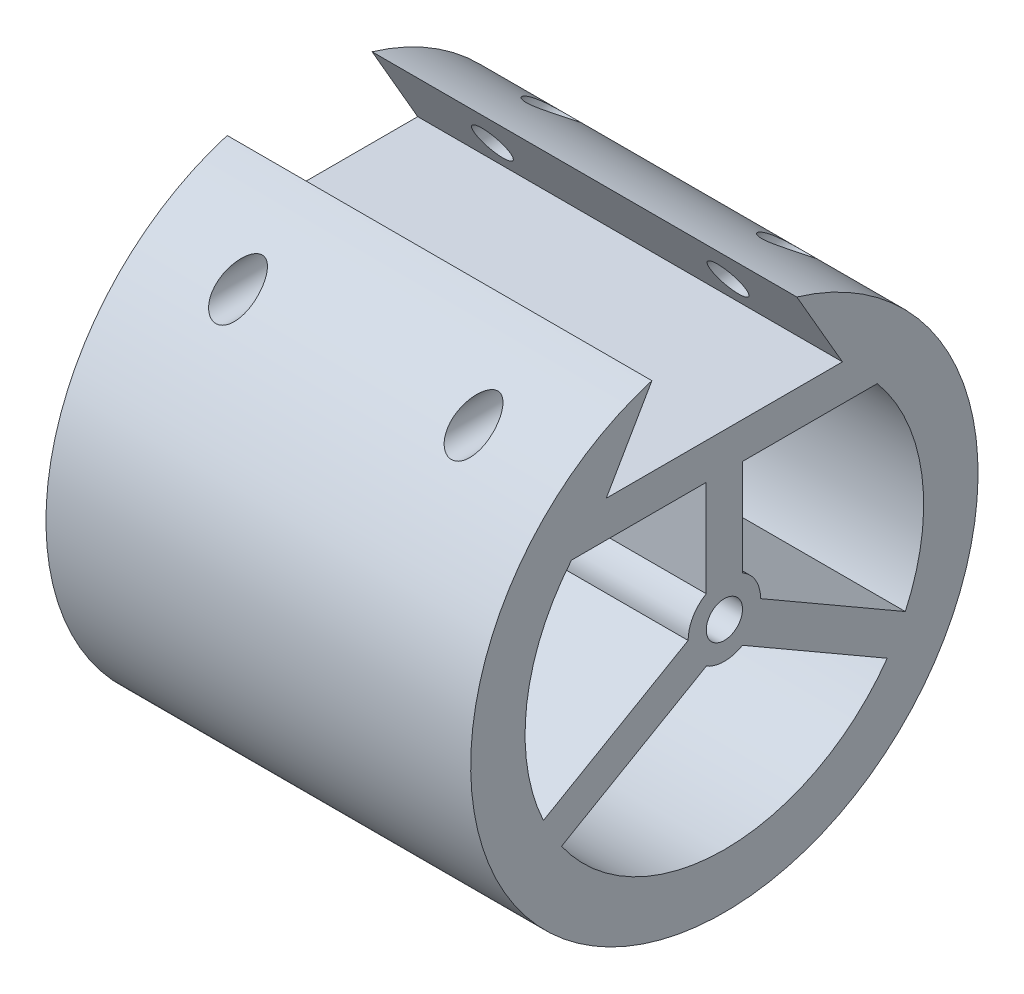
SolidWorks part; units mm, degrees
ref_plane "Front Plane" through (0, 0, 0) normal (0, 0, 1) x (1, 0, 0)
ref_plane "Top Plane" through (0, 0, 0) normal (0, 1, 0) x (1, 0, 0)
ref_plane "Right Plane" through (0, 0, 0) normal (1, 0, 0) x (0, 0, -1)
sketch "Sketch1" plane through (0, 0, 0) normal (1, 0, 0) x (0, 0, -1)
  circle A0 centre (0, 0) radius 14
  circle A1 centre (0, 0) radius 11
  dimension "D1" = 28
  dimension "D2" = 3
extrude "Boss-Extrude1" add sketch "Sketch1" along normal blind 11.72 and the other way blind 11.72
sketch "Sketch2" plane through (0, 0, 0) normal (1, 0, 0) x (0, 0, -1)
  line L0 (0, -1000) -> (0, 49000) construction
  line L1 (-997.3506, 13.4164) -> (49002.6494, 13.4164) construction
  line L2 (-998.4509, 11) -> (49001.5491, 11) construction
  line L3 (-6.5172, 9.0564) -> (6.5172, 9.0564)
  line L4 (6.5172, 9.0564) -> (4, 13.4164)
  line L6 (-4, 13.4164) -> (-6.5172, 9.0564)
  circle A0 centre (0, 0) radius 14 construction
  arc A1 (-4, 13.4164) -> (4, 13.4164) centre (0, 0) cw
  circle A2 centre (0, 0) radius 11 construction
  dimension "D1" = 60
  dimension "D2" = 8
  dimension "D3" = 4.36
extrude "Cut-Extrude1" cut sketch "Sketch2" against normal through all and the other way through all
sketch "Sketch3" plane through (0, 0, 0) normal (1, 0, 0) x (0, 0, -1)
  line L0 (-12.5934, -6.1161) -> (-11.5934, -7.8481)
  line L1 (-11.5934, -7.8481) -> (-1, -1.7321)
  line L2 (-1000, 0) -> (49000, 0) construction
  line L3 (1, -1.7321) -> (11.5934, -7.8481)
  line L4 (11.5934, -7.8481) -> (12.5934, -6.1161)
  line L5 (12.5934, -6.1161) -> (2, 0)
  line L6 (-12.5934, -6.1161) -> (-2, 0)
  line L7 (-8.4384, 9.0564) -> (8.4384, 9.0564)
  line L8 (8.4384, 9.0564) -> (8.4384, 7.0564)
  line L9 (8.4384, 7.0564) -> (1, 7.0564)
  line L10 (-8.4384, 9.0564) -> (-8.4384, 7.0564)
  line L11 (-8.4384, 7.0564) -> (-1, 7.0564)
  line L12 (-6.5172, 9.0564) -> (-6.2435, 9.0564) construction
  line L13 (-1, 7.0564) -> (-1, 1.7321)
  line L14 (1, 7.0564) -> (1, 1.7321)
  line L15 (0, -1000) -> (0, 49000) construction
  arc A2 (1, 1.7321) -> (2, 0) centre (0, 0) cw
  arc A3 (1, -1.7321) -> (-1, -1.7321) centre (0, 0) cw
  circle A4 centre (0, 0) radius 1
  arc A5 (-6.2435, 9.0564) -> (6.2435, 9.0564) centre (0, 0) ccw construction
  arc A6 (-2, 0) -> (-1, 1.7321) centre (0, 0) cw
  arc A7 (-4, 13.4164) -> (4, 13.4164) centre (0, 0) ccw construction
  point P20 (1, 4.3942)
  dimension "D3" = 60
  dimension "D4" = 2
  dimension "D1" = 2
  dimension "D2" = 2
  dimension "D5" = 2
  dimension "D6" = 2
  dimension "D7" = 2
extrude "Boss-Extrude2" add sketch "Sketch3" along normal up to surface (11.72 mm away) and the other way up to surface (11.72 mm away) up to face at (11.72, 2.5976, 0) other way up to face at (-11.72, 2.5976, 0)
sketch "Sketch4" plane through (0, 0, 0) normal (0, 0, 1) x (1, 0, 0)
  line L0 (0, -1000) -> (0, 49000) construction
  line L2 (-11.72, 9.0564) -> (11.72, 9.0564) construction
  circle A0 centre (-6.5, 10.9564) radius 1
  circle A1 centre (6.5, 10.9564) radius 1
  dimension "D1" = 2
  dimension "D3" = 1.9
  dimension "D2" = 13
extrude "Cut-Extrude2" cut sketch "Sketch4" against normal through all and the other way through all
